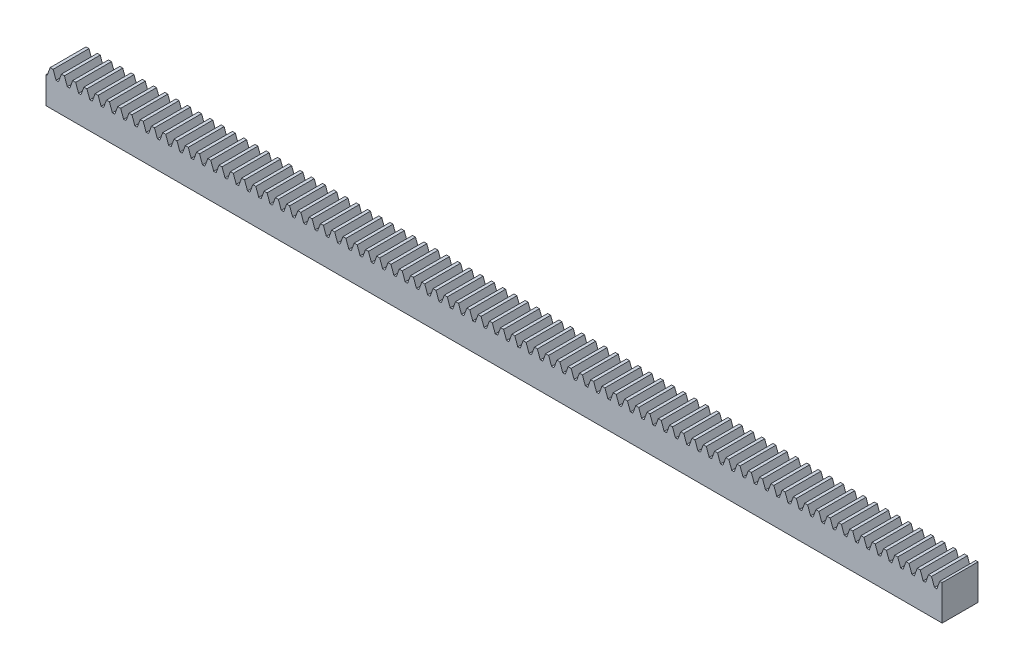
SolidWorks part; units mm, degrees
ref_plane "Front" through (0, 0, 0) normal (0, 0, 1) x (1, 0, 0)
ref_plane "Top" through (0, 0, 0) normal (0, 1, 0) x (1, 0, 0)
ref_plane "Right" through (0, 0, 0) normal (1, 0, 0) x (0, 0, -1)
sketch "Ritning 1" plane through (0, 0, 0) normal (0, 0, 1) x (1, 0, 0)
  line L1 (-124.1, -4.9) -> (125.9, -4.9)
  line L2 (-124.1, -4.9) -> (-124.1, 4.9)
  line L3 (-124.1, 4.9) -> (125.9, 4.9)
  line L4 (125.9, -4.9) -> (125.9, 4.9)
  dimension "D1" = 125.9
  dimension "D2" = 124.1
  dimension "D3" = 4.9
  dimension "D4" = 4.9
extrude "Kuggstångsämne" add sketch "Ritning 1" along normal blind 10
sketch "Ritning 2" plane through (0, 0, 10) normal (0, 0, 1) x (1, 0, 0)
  line L0 (-124.4383, 2.65) -> (-123.7617, 2.65)
  line L1 (-125.2572, 4.9) -> (-124.1, 6.0572)
  line L2 (125.9, -4.9) -> (125.9, 4.9) construction
  line L3 (-124.1, -4.9) -> (125.9, -4.9) construction
  line L7 (-124.1, 6.0572) -> (-122.9428, 4.9)
  line L9 (-122.9428, 4.9) -> (-123.7617, 2.65)
  spline S0 degree 3 poles (-125.2572, 4.9) (-124.9842, 4.15) (-124.7113, 3.4) (-124.4383, 2.65) knots 0 0 0 0 1 1 1 1
  dimension "D1" = 248.8428
  dimension "D2" = 249.6617
  dimension "D3" = 250
  dimension "D4" = 250.3383
  dimension "D5" = 7.55
  dimension "D6" = 9.8
extrude "Kugglucka" cut sketch "Ritning 2" against normal blind 10
ref_axis "Axis" through (125.9, 4.9, 10) along (-1, 0, 0)
pattern_linear "LPattern" count 80 spacing 3.1416 along (1, 0, 0) of "Kugglucka"
